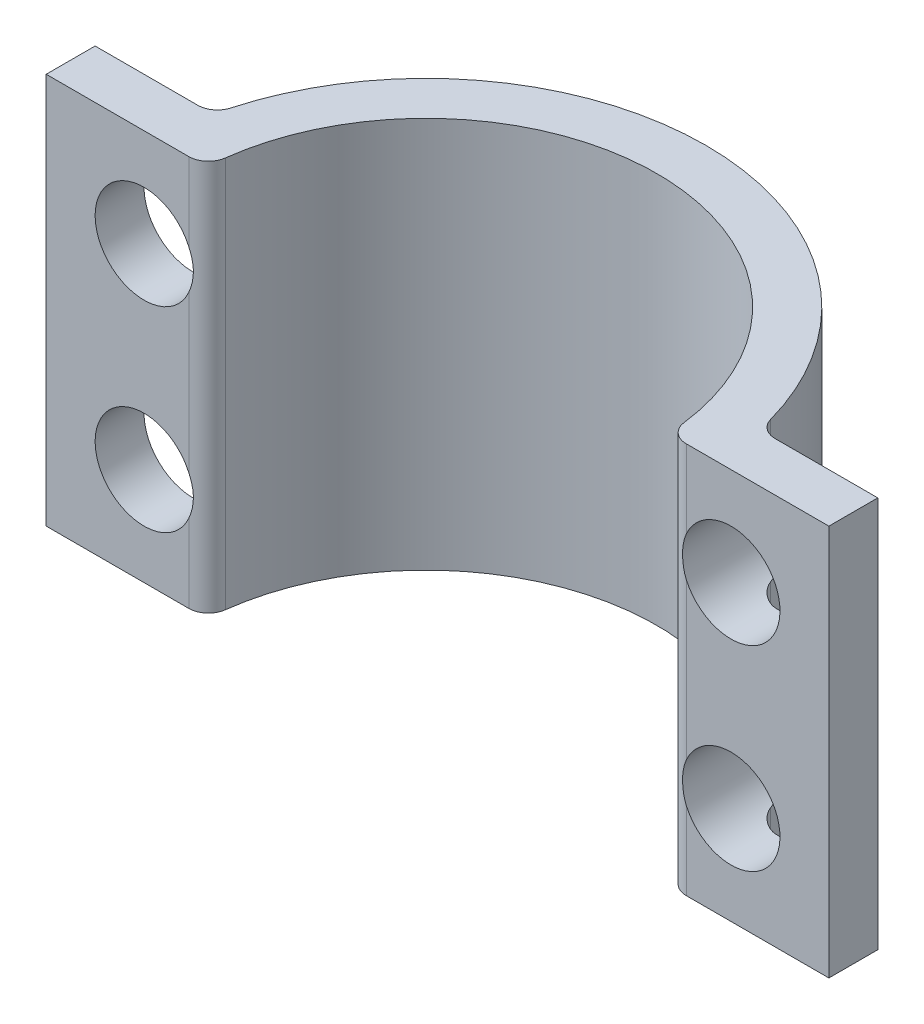
SolidWorks part; units mm, degrees
ref_plane "Front Plane" through (0, 0, 0) normal (0, 0, 1) x (1, 0, 0)
ref_plane "Top Plane" through (0, 0, 0) normal (0, 1, 0) x (1, 0, 0)
ref_plane "Right Plane" through (0, 0, 0) normal (1, 0, 0) x (0, 0, -1)
sketch "Sketch2" plane through (0, 0, 0) normal (0, 1, 0) x (1, 0, 0)
  line L0 (0, 0) -> (-10.4194, 0)
  line L1 (-10.4194, 0) -> (-10.4194, 3.175)
  line L2 (-10.4194, 3.175) -> (-2.7628, 3.175)
  line L3 (32.7241, 3.175) -> (40.3806, 3.175)
  line L4 (40.3806, 3.175) -> (40.3806, 0)
  line L5 (40.3806, 0) -> (29.9613, 0)
  line L6 (14.9806, 0.1727) -> (14.9806, 50000.1727) construction
  circle A0 centre (14.9806, -0.762) radius 15 construction
  arc A1 (29.9613, 0) -> (0, 0) centre (14.9806, -0.762) ccw
  arc A2 (32.7241, 3.175) -> (-2.7628, 3.175) centre (14.9806, -0.762) ccw
  point P5 (-4.0694, 0)
  point P8 (34.0306, 0)
  dimension "D1" = 15
  dimension "D2" = 3.175
  dimension "D3" = 38.1
  dimension "D4" = 3.175
  dimension "D5" = 6.35
  dimension "D6" = 0.762
extrude "Boss-Extrude1" add sketch "Sketch2" against normal blind 25.4
sketch "Sketch3" plane through (0, 0, 0) normal (0, 0, 1) x (1, 0, 0)
  line L0 (14.9806, 0) -> (14.9806, -50000) construction
  line L1 (29.9613, 0) -> (0, 0) construction
  line L2 (-10.4194, 0) -> (0, 0) construction
  circle A0 centre (-4.0694, -6.35) radius 3.175
  circle A1 centre (34.0306, -6.35) radius 3.175
  circle A2 centre (-4.0694, -19.05) radius 3.175
  circle A3 centre (34.0306, -19.05) radius 3.175
  point P8 (14.9806, 0)
  point P15 (0, 0)
  point P16 (0, 0)
  point P17 (0, 0)
  point P18 (0, 0)
  dimension "D1" = 6.35
  dimension "D4" = 12.7
  dimension "D2" = 38.1
  dimension "D3" = 6.35
extrude "Cut-Extrude1" cut sketch "Sketch3" against normal through all
fillet "Fillet1" radius 1.27 8 edges at (32.7241, -23.6719, -3.175) (32.7241, -12.7, -3.175) (32.7241, -1.7281, -3.175) (-2.7628, -1.7281, -3.175) (-2.7628, -23.6719, -3.175) (-2.7628, -12.7, -3.175) (29.9613, -12.7, 0) (0, -12.7, 0)
